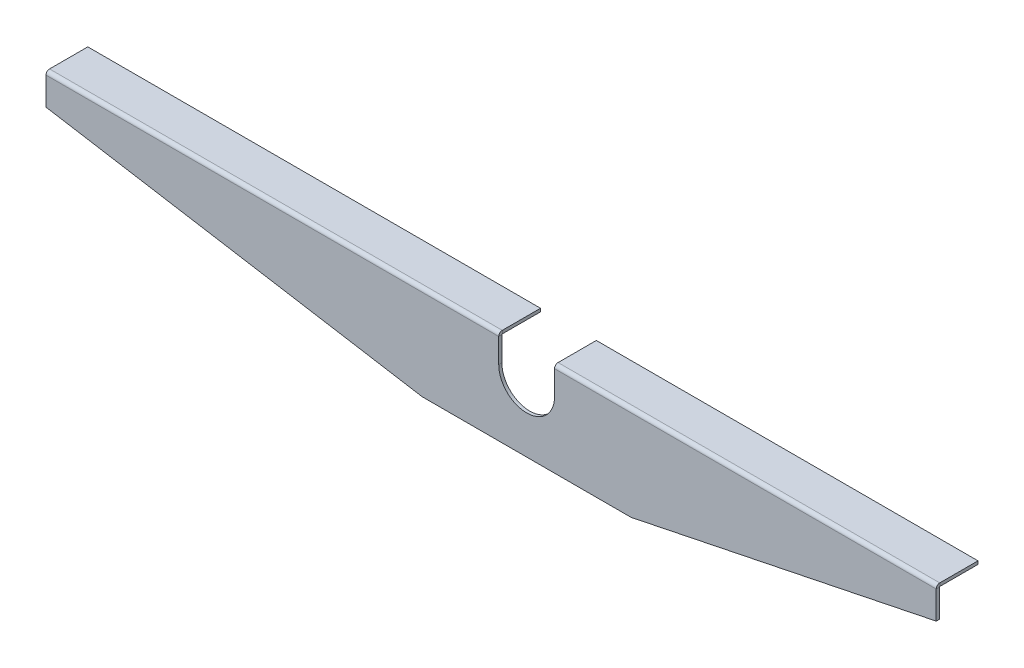
SolidWorks part; units mm, degrees
note: The reader was unsure of these and kept them because the rebuilt part matched: flange length of "Edge-Flange1".
material "ASTM A36 Steel"
ref_plane "Front Plane" through (0, 0, 0) normal (0, 0, 1) x (1, 0, 0)
ref_plane "Top Plane" through (0, 0, 0) normal (0, 1, 0) x (1, 0, 0)
ref_plane "Right Plane" through (0, 0, 0) normal (1, 0, 0) x (0, 0, -1)
sketch "Sketch1" plane through (0, 0, 0) normal (0, 0, 1) x (1, 0, 0)
  line L0 (13.35, 0) -> (13.35, 13.35)
  line L1 (13.35, 13.35) -> (196, 13.35)
  line L2 (196, 13.35) -> (196, -1.65)
  line L3 (196, -1.65) -> (50, -31.65)
  line L4 (50, -31.65) -> (-50, -31.65)
  line L5 (-50, -31.65) -> (-230, -1.65)
  line L6 (-230, -1.65) -> (-230, 13.35)
  line L7 (-230, 13.35) -> (-13.35, 13.35)
  line L8 (-13.35, 13.35) -> (-13.35, 0)
  arc A0 (-13.35, 0) -> (13.35, 0) centre (0, 0) ccw
  point P1 (0, -31.65)
  dimension "D1" = 26.7
  dimension "D2" = 100
  dimension "D3" = 0
  dimension "D4" = 15
  dimension "D5" = 15
  dimension "D6" = 230
  dimension "D7" = 196
  dimension "D8" = 45
base flange "Base-Flange1" sketch "Sketch1" thickness 1.5 reverse thickness direction no parameters "D1"=0.2
edge flange "Edge-Flange1" sketch "Sketch10" flange profiles "Sketch10", "Sketch11" flange angle 90 flange length 20 flange position material inside bend radius 0.2 thickness 1.5 relief rectangular parameters "D6"=10, "D8"=1
sketch "Sketch10" plane through (0, 13.35, -1.5) normal (0, -1, 0) x (-1, 0, 0)
  line L2 (13.35, 0) -> (13.35, 18.5)
  line L3 (13.35, 18.5) -> (230, 18.5)
  line L4 (230, 18.5) -> (230, 0)
  line L5 (230, 0) -> (13.35, 0) construction
  line L6 (230, 0) -> (13.35, 0)
sketch "Sketch11" plane through (0, 13.35, -1.5) normal (0, -1, 0) x (-1, 0, 0)
  line L2 (-196, 0) -> (-196, 18.5)
  line L3 (-196, 18.5) -> (-13.35, 18.5)
  line L4 (-13.35, 18.5) -> (-13.35, 0)
  line L5 (-13.35, 0) -> (-196, 0) construction
  line L6 (-13.35, 0) -> (-196, 0)
bend "EdgeBend1" bend radius 0.2 bend angle 90 parameters "D5"=1
bend "EdgeBend2" bend radius 0.2 bend angle 90 parameters "D5"=2
sketch "Bend-Lines1" [suppressed] plane through (0, 0, 0) normal (0, 1, 0) x (1, 0, 0)
sketch "Bounding-Box1" [suppressed] plane through (0, 0, 0) normal (0, 1, 0) x (1, 0, 0)
sheet metal parameters "Sheet-Metal1" thickness 1.5 parameters "D1"=0.2
flat pattern "Flat-Pattern1" [suppressed]
sketch "Bend-Lines2" plane through (0, 0, 0) normal (0, 1, 0) x (1, 0, 0)
sketch3d "Bounding-Box2" [suppressed]
  line L0 (350, -31.65, 0) -> (-350, -31.65, 0) construction
  line L1 (350, 13.35, 0) -> (-350, 13.35, 0) construction
  line L2 (350, -31.65, 0) -> (350, 13.35, 0) construction
  line L3 (-350, -31.65, 0) -> (-350, 13.35, 0) construction
sheet metal parameters "Sheet-Metal2" thickness 1.5 parameters "D1"=0.2
flat pattern "Flat-Pattern1"
sketch "Bend-Lines2" plane through (0, 0, 0) normal (0, 0, 1) x (1, 0, 0)
  line L0 (196, 12.3961) -> (13.35, 12.3961) construction
  line L1 (-13.35, 12.3961) -> (-230, 12.3961) construction
  line L2 (196, 12.3961) -> (13.35, 12.3961) construction
  line L3 (-13.35, 12.3961) -> (-230, 12.3961) construction
sketch3d "Bounding-Box2" [suppressed]
  line L0 (-230, -31.65, 0) -> (196, -31.65, 0) construction
  line L1 (-230, 31.4423, 0) -> (196, 31.4423, 0) construction
  line L2 (-230, -31.65, 0) -> (-230, 31.4423, 0) construction
  line L3 (196, -31.65, 0) -> (196, 31.4423, 0) construction
bend of the flat pattern "Flatten-<EdgeBend1>1"
bend of the flat pattern "Flatten-<EdgeBend2>1"
